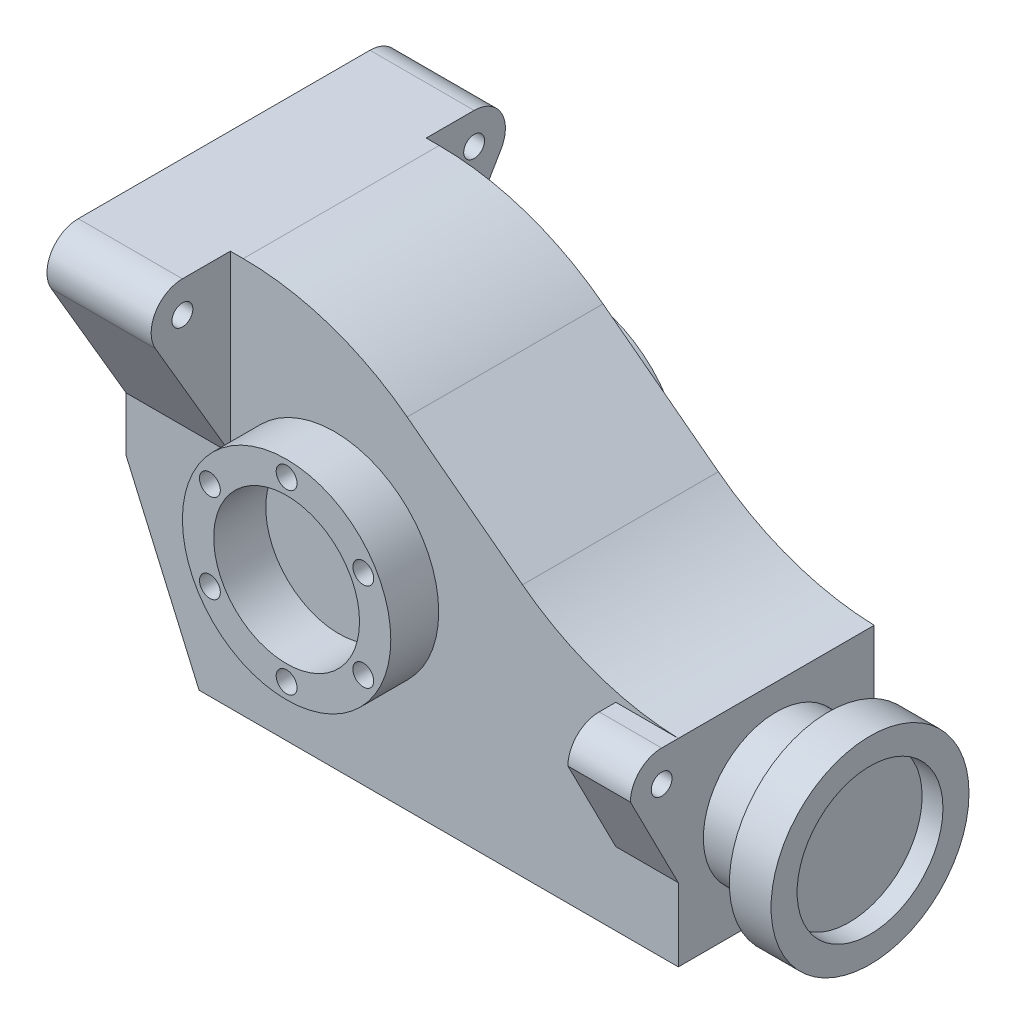
SolidWorks part; units mm, degrees
ref_plane "Płaszczyzna przednia" through (0, 0, 0) normal (0, 0, 1) x (1, 0, 0)
ref_plane "Płaszczyzna górna" through (0, 0, 0) normal (0, 1, 0) x (1, 0, 0)
ref_plane "Płaszczyzna prawa" through (0, 0, 0) normal (1, 0, 0) x (0, 0, -1)
sketch "Szkic1" plane through (0, 0, 0) normal (0, 0, 1) x (1, 0, 0)
  line L0 (-35, 190) -> (65, 190)
  line L1 (65, 190) -> (190, 95)
  line L2 (190, 95) -> (230, 95)
  line L3 (230, 95) -> (230, 0)
  line L4 (230, 0) -> (0, 0)
  line L7 (-35, 190) -> (-35, 80)
  line L8 (-35, 80) -> (0, 0)
  dimension "D1" = 265
  dimension "D2" = 190
  dimension "D3" = 95
  dimension "D4" = 80
  dimension "D5" = 230
  dimension "D6" = 100
  dimension "D7" = 40
extrude "Dodanie-wyciągnięcie1" add sketch "Szkic1" along normal mid plane 94 contours L1 L2 L3 L4 L8 L7 L0
sketch "Szkic2" plane through (230, 0, 0) normal (1, 0, 0) x (0, 0, -1)
  line L0 (-47, 95) -> (47, 0) construction
  line L1 (47, 95) -> (-47, 0) construction
  line L2 (-47, 0) -> (47, 0) construction
  circle A0 centre (0, 47.5) radius 35
  point P13 (0, 47.5)
  dimension "D1" = 70
extrude "Dodanie-wyciągnięcie2" add sketch "Szkic2" along normal blind 25 separate body
sketch "Szkic3" plane through (255, 0, 0) normal (1, 0, 0) x (0, 0, -1)
  circle A0 centre (0, 47.5) radius 47.5
  circle A1 centre (0, 47.5) radius 35 construction
  dimension "D1" = 95
extrude "Dodanie-wyciągnięcie3" add sketch "Szkic3" along normal blind 20
sketch "Szkic4" plane through (275, 0, 0) normal (1, 0, 0) x (0, 0, -1)
  circle A0 centre (0, 47.5) radius 35
  circle A1 centre (0, 47.5) radius 47.5 construction
  dimension "D1" = 70
sketch "Szkic7" plane through (0, 0, 47) normal (0, 0, 1) x (1, 0, 0)
  line L0 (-35, 190) -> (-35, 80) construction
  line L1 (-35, 190) -> (65, 190) construction
  circle A0 centre (65, 90) radius 50
  dimension "D1" = 100
  dimension "D2" = 100
  dimension "D3" = 100
extrude "Dodanie-wyciągnięcie5" add sketch "Szkic7" along normal blind 23
sketch "Szkic8" plane through (0, 0, 70) normal (0, 0, 1) x (1, 0, 0)
  circle A0 centre (65, 90) radius 35
  dimension "D1" = 70
extrude "Wytnij-wyciągnięcie1" cut sketch "Szkic8" against normal blind 25
sketch "Szkic9" plane through (0, 0, 70) normal (0, 0, 1) x (1, 0, 0)
  line L0 (65, 90) -> (65, 132.5) construction
  circle A0 centre (65, 132.5) radius 5
  circle A1 centre (101.8061, 111.25) radius 5
  circle A2 centre (65, 90) radius 35 construction
  circle A3 centre (65, 90) radius 35
  circle A4 centre (101.8061, 68.75) radius 5
  circle A5 centre (65, 47.5) radius 5
  circle A6 centre (28.1939, 68.75) radius 5
  circle A7 centre (28.1939, 111.25) radius 5
  dimension "D1" = 10
  dimension "D2" = 42.5
  dimension "D3" = 6
  dimension "D4" = 42.5
extrude "Wytnij-wyciągnięcie2" cut sketch "Szkic9" against normal blind 15 contours A0 | A1 | A4 | A5 | A6 | A7
sketch "Szkic12" plane through (-35, 0, 0) normal (-1, 0, 0) x (0, 0, 1)
  line L0 (-70, 190) -> (70, 190)
  line L1 (47, 190) -> (-47, 190) construction
  line L2 (-82.9419, 167.4166) -> (-20, 60)
  line L4 (47, 0) -> (-47, 0) construction
  line L5 (-20, 60) -> (20, 60)
  line L6 (0, 190) -> (0, 60) construction
  line L7 (82.9419, 167.4166) -> (20, 60)
  circle A0 centre (-70, 175) radius 5
  arc A1 (-70, 190) -> (-82.9419, 167.4166) centre (-70, 175) ccw
  arc A2 (70, 190) -> (82.9419, 167.4166) centre (70, 175) cw
  circle A3 centre (70, 175) radius 5
  line M4 (-47, 190) -> (-47, 80)
  line M5 (-47, 80) -> (47, 80)
  line M6 (47, 80) -> (47, 190)
  line M7 (47, 190) -> (-47, 190)
  dimension "D1" = 10
  dimension "D2" = 30
  dimension "D4" = 20
  dimension "D5" = 70
  dimension "D3" = 60
extrude "Dodanie-wyciągnięcie6" add sketch "Szkic12" against normal blind 50 contours L0 A1 L2 A0 M4 | L6 L0 L2 M4 M5 | L6 L7 M7 M5 M6 | A2 L0 L7 A3 M6 | L6 L5 L7 M5 | L6 L2 L5 M5 region at (-35, 159.5519, -61.1328) region at (-35, 136.8562, -22.7622) region at (-35, 136.8562, 22.7622) region at (-35, 159.5519, 61.1328) region at (-35, 70.7553, 13.1511) region at (-35, 70.7553, -13.1511)
mirror "Lustro1" about plane through (0, 0, 0) normal (0, 0, 1) of "Wytnij-wyciągnięcie2", "Wytnij-wyciągnięcie1", "Dodanie-wyciągnięcie5"
fillet "Zaokrąglenie2" radius 130 1 edges at (65, 190, 0)
fillet "Zaokrąglenie3" radius 130 1 edges at (190, 95, 0)
extrude "Wytnij-wyciągnięcie3" cut sketch "Szkic4" against normal blind 10
sketch "Szkic13" plane through (0, 0, 47) normal (0, 0, 1) x (1, 0, 0)
  line L0 (230, 95) -> (230, 0) construction
  line L1 (230, 95) -> (200, 95)
  line L2 (230, 95) -> (230, 35)
  line L3 (230, 35) -> (200, 35)
  line L4 (200, 95) -> (200, 35)
  dimension "D1" = 60
  dimension "D2" = 30
sketch "Szkic14" plane through (0, 0, 70) normal (0, 0, 1) x (1, 0, 0)
  line L1 (200, 95) -> (230, 95)
  line L2 (200, 95) -> (200, 60)
  line L3 (200, 60) -> (230, 60)
  line L4 (230, 95) -> (230, 60)
  line L5 (230, 95) -> (230, 35) construction
  dimension "D1" = 35
loft "Wyciągnięcie po profilach1" add profiles "Szkic13", "Szkic14" connector at (230, 35, 47) connector at (230, 60, 70)
sketch "Szkic15" plane through (230, 0, 0) normal (1, 0, 0) x (0, 0, -1)
  line L0 (-47, 95) -> (-70, 95) construction
  line L1 (-70, 60) -> (-70, 95) construction
  line L5 (-70, 80) -> (-70, 95)
  line L6 (-70, 95) -> (-55, 95)
  arc A0 (-55, 95) -> (-70, 80) centre (-55, 80) ccw
  dimension "D1" = 30
extrude "Wytnij-wyciągnięcie4" cut sketch "Szkic15" against normal up to next (30 mm away)
sketch "Szkic19" plane through (230, 0, 0) normal (1, 0, 0) x (0, 0, -1)
  line L0 (-70, 80) -> (-47, 35)
  line L1 (-47, 35) -> (-70, 60)
  line L2 (-70, 60) -> (-70, 80)
extrude "Wytnij-wyciągnięcie6" cut sketch "Szkic19" against normal up to next (30 mm away) contours L0 L1 L2
sketch "Szkic20" plane through (230, 0, 0) normal (1, 0, 0) x (0, 0, -1)
  circle A0 centre (-55, 80) radius 5
  arc A1 (-55, 95) -> (-70, 80) centre (-55, 80) ccw construction
  dimension "D1" = 10
extrude "Wytnij-wyciągnięcie7" cut sketch "Szkic20" against normal up to next (30 mm away)
